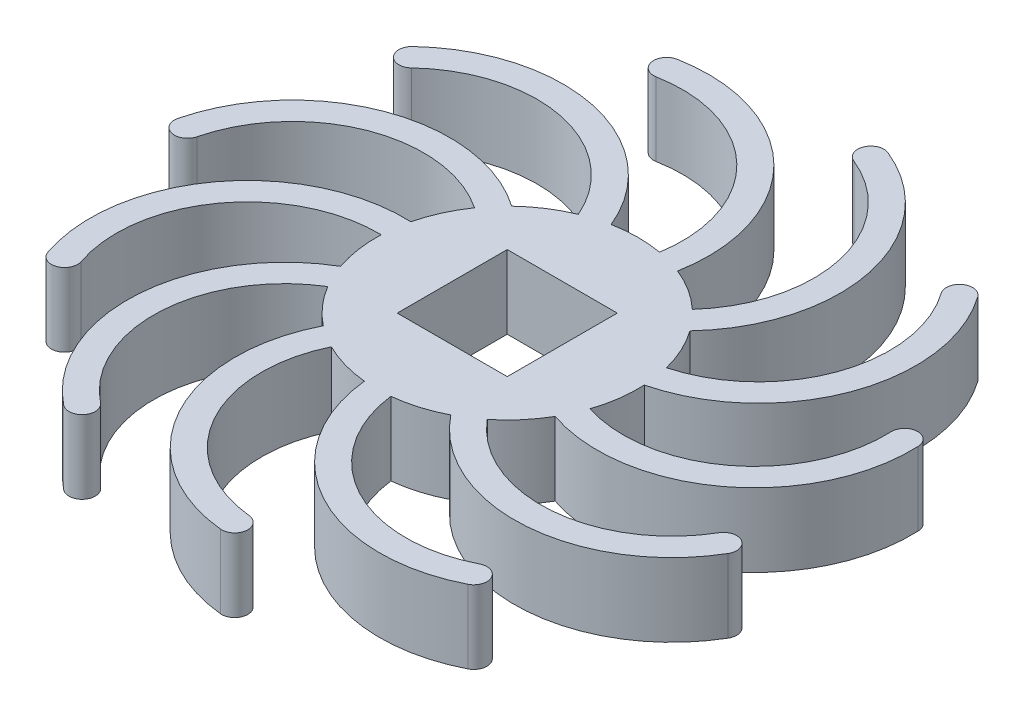
SolidWorks part; units mm, degrees
ref_plane "Front Plane" through (0, 0, 0) normal (0, 0, 1) x (1, 0, 0)
ref_plane "Top Plane" through (0, 0, 0) normal (0, 1, 0) x (1, 0, 0)
ref_plane "Right Plane" through (0, 0, 0) normal (1, 0, 0) x (0, 0, -1)
sketch "Sketch1" plane through (0, 0, 0) normal (0, 1, 0) x (1, 0, 0)
  line L0 (0, 5) -> (5.1962, 8) construction
  line L1 (-2.1, 2.1) -> (2.1, 2.1)
  line L2 (-2.1, 2.1) -> (-2.1, -2.1)
  line L3 (-2.1, -2.1) -> (2.1, -2.1)
  line L4 (2.1, 2.1) -> (2.1, -2.1)
  line L5 (0, -2.1) -> (0, 2.1) construction
  line L6 (-2.1, 0) -> (2.1, 0) construction
  line L7 (5.1962, 8) -> (5.1962, 7.3) construction
  line L8 (5.1962, 7.3) -> (0, 4.3) construction
  line L9 (0, 4.3) -> (0, 5) construction
  line L10 (2.1443, 3.7451) -> (2.4943, 4.3513) construction
  line L11 (2.4943, 4.3513) -> (8.4943, 4.3513) construction
  line L12 (8.4943, 4.3513) -> (8.1443, 3.7451) construction
  line L13 (8.1443, 3.7451) -> (2.1443, 3.7451) construction
  line L14 (3.7239, 2.1924) -> (4.3301, 2.5424) construction
  line L15 (4.3301, 2.5424) -> (9.5263, -0.4576) construction
  line L16 (9.5263, -0.4576) -> (8.9201, -0.8076) construction
  line L17 (8.9201, -0.8076) -> (3.7239, 2.1924) construction
  line L18 (4.3155, 0.058) -> (5.0155, 0.058) construction
  line L19 (5.0155, 0.058) -> (8.0155, -5.1382) construction
  line L20 (8.0155, -5.1382) -> (7.3155, -5.1382) construction
  line L21 (7.3155, -5.1382) -> (4.3155, 0.058) construction
  line L22 (3.7607, -2.0863) -> (4.3669, -2.4363) construction
  line L23 (4.3669, -2.4363) -> (4.3669, -8.4363) construction
  line L24 (4.3669, -8.4363) -> (3.7607, -8.0863) construction
  line L25 (3.7607, -8.0863) -> (3.7607, -2.0863) construction
  line L26 (2.208, -3.6659) -> (2.558, -4.2721) construction
  line L27 (2.558, -4.2721) -> (-0.442, -9.4683) construction
  line L28 (-0.442, -9.4683) -> (-0.792, -8.8621) construction
  line L29 (-0.792, -8.8621) -> (2.208, -3.6659) construction
  line L30 (0.0735, -4.2576) -> (0.0735, -4.9576) construction
  line L31 (0.0735, -4.9576) -> (-5.1226, -7.9576) construction
  line L32 (-5.1226, -7.9576) -> (-5.1226, -7.2576) construction
  line L33 (-5.1226, -7.2576) -> (0.0735, -4.2576) construction
  line L34 (-2.0708, -3.7027) -> (-2.4208, -4.3089) construction
  line L35 (-2.4208, -4.3089) -> (-8.4208, -4.3089) construction
  line L36 (-8.4208, -4.3089) -> (-8.0708, -3.7027) construction
  line L37 (-8.0708, -3.7027) -> (-2.0708, -3.7027) construction
  line L38 (-3.6504, -2.15) -> (-4.2566, -2.5) construction
  line L39 (-4.2566, -2.5) -> (-9.4528, 0.5) construction
  line L40 (-9.4528, 0.5) -> (-8.8465, 0.85) construction
  line L41 (-8.8465, 0.85) -> (-3.6504, -2.15) construction
  line L42 (-4.242, -0.0155) -> (-4.942, -0.0155) construction
  line L43 (-4.942, -0.0155) -> (-7.942, 5.1806) construction
  line L44 (-7.942, 5.1806) -> (-7.242, 5.1806) construction
  line L45 (-7.242, 5.1806) -> (-4.242, -0.0155) construction
  line L46 (-3.6872, 2.1288) -> (-4.2934, 2.4788) construction
  line L47 (-4.2934, 2.4788) -> (-4.2934, 8.4788) construction
  line L48 (-4.2934, 8.4788) -> (-3.6872, 8.1288) construction
  line L49 (-3.6872, 8.1288) -> (-3.6872, 2.1288) construction
  line L50 (-2.1345, 3.7084) -> (-2.4845, 4.3146) construction
  line L51 (-2.4845, 4.3146) -> (0.5155, 9.5107) construction
  line L52 (0.5155, 9.5107) -> (0.8655, 8.9045) construction
  line L53 (0.8655, 8.9045) -> (-2.1345, 3.7084) construction
  circle A0 centre (0, 0) radius 5
  point P62 (0.0368, 0.0212)
  dimension "D1" = 10
  dimension "D2" = 4.2
  dimension "D3" = 4.2
  dimension "D4" = 0.7
  dimension "D5" = 120
  dimension "D6" = 6
  dimension "D7" = 12
extrude "Boss-Extrude1" add sketch "Sketch1" along normal blind 2.8
sketch "Sketch2" plane through (0, 0, 0) normal (0, 1, 0) x (1, 0, 0)
  line L0 (0, -5) -> (7.99, -9.613) construction
  line L1 (7.99, -9.613) -> (7.99, -8.9202) construction
  line L2 (7.99, -8.9202) -> (0, -4.3072) construction
  line L3 (0, -4.3072) -> (0, -5) construction
  line L4 (0, 0) -> (0, -5) construction
  line L5 (-2.1536, -3.7301) -> (-2.5, -4.3301) construction
  line L6 (-2.1, -2.1) -> (2.1, -2.1) construction
  line L7 (-2.1, -2.1) -> (-2.1, 2.1) construction
  line L8 (-2.1, 2.1) -> (2.1, 2.1) construction
  line L9 (2.1, -2.1) -> (2.1, 2.1) construction
  line L10 (0, 2.1) -> (0, -2.1) construction
  line L11 (-2.1, 0) -> (2.1, 0) construction
  line L12 (-2.5, -4.3301) -> (2.113, -12.3201) construction
  line L13 (2.113, -12.3201) -> (2.4594, -11.7201) construction
  line L14 (2.4594, -11.7201) -> (-2.1536, -3.7301) construction
  line L15 (-3.7301, -2.1536) -> (-4.3301, -2.5) construction
  line L16 (-4.3301, -2.5) -> (-4.3301, -11.726) construction
  line L17 (-4.3301, -11.726) -> (-3.7301, -11.3796) construction
  line L18 (-3.7301, -11.3796) -> (-3.7301, -2.1536) construction
  line L19 (-4.3072, 0) -> (-5, 0) construction
  line L20 (-5, 0) -> (-9.613, -7.99) construction
  line L21 (-9.613, -7.99) -> (-8.9202, -7.99) construction
  line L22 (-8.9202, -7.99) -> (-4.3072, 0) construction
  line L23 (-3.7301, 2.1536) -> (-4.3301, 2.5) construction
  line L24 (-4.3301, 2.5) -> (-12.3201, -2.113) construction
  line L25 (-12.3201, -2.113) -> (-11.7201, -2.4594) construction
  line L26 (-11.7201, -2.4594) -> (-3.7301, 2.1536) construction
  line L27 (-2.1536, 3.7301) -> (-2.5, 4.3301) construction
  line L28 (-2.5, 4.3301) -> (-11.726, 4.3301) construction
  line L29 (-11.726, 4.3301) -> (-11.3796, 3.7301) construction
  line L30 (-11.3796, 3.7301) -> (-2.1536, 3.7301) construction
  line L31 (0, 4.3072) -> (0, 5) construction
  line L32 (0, 5) -> (-7.99, 9.613) construction
  line L33 (-7.99, 9.613) -> (-7.99, 8.9202) construction
  line L34 (-7.99, 8.9202) -> (0, 4.3072) construction
  line L35 (2.1536, 3.7301) -> (2.5, 4.3301) construction
  line L36 (2.5, 4.3301) -> (-2.113, 12.3201) construction
  line L37 (-2.113, 12.3201) -> (-2.4594, 11.7201) construction
  line L38 (-2.4594, 11.7201) -> (2.1536, 3.7301) construction
  line L39 (3.7301, 2.1536) -> (4.3301, 2.5) construction
  line L40 (4.3301, 2.5) -> (4.3301, 11.726) construction
  line L41 (4.3301, 11.726) -> (3.7301, 11.3796) construction
  line L42 (3.7301, 11.3796) -> (3.7301, 2.1536) construction
  line L43 (4.3072, 0) -> (5, 0) construction
  line L44 (5, 0) -> (9.613, 7.99) construction
  line L45 (9.613, 7.99) -> (8.9202, 7.99) construction
  line L46 (8.9202, 7.99) -> (4.3072, 0) construction
  line L47 (3.7301, -2.1536) -> (4.3301, -2.5) construction
  line L48 (4.3301, -2.5) -> (12.3201, 2.113) construction
  line L49 (12.3201, 2.113) -> (11.7201, 2.4594) construction
  line L50 (11.7201, 2.4594) -> (3.7301, -2.1536) construction
  line L51 (2.1536, -3.7301) -> (2.5, -4.3301) construction
  line L52 (2.5, -4.3301) -> (11.726, -4.3301) construction
  line L53 (11.726, -4.3301) -> (11.3796, -3.7301) construction
  line L54 (11.3796, -3.7301) -> (2.1536, -3.7301) construction
  line L55 (7.99, -9.2666) -> (0, -4.6536) construction
  line L56 (3.995, -6.9601) -> (5.495, -4.362) construction
  circle A0 centre (0, 0) radius 5 construction
  arc A1 (0, -4.6536) -> (7.99, -9.2666) centre (5.495, -4.362) ccw construction
  arc A2 (-0.4993, -4.6801) -> (8.2167, -9.7123) centre (5.495, -4.362) ccw
  arc A3 (0.4993, -4.6271) -> (7.7633, -8.821) centre (5.495, -4.362) ccw
  arc A4 (0.4993, -4.6271) -> (-0.4993, -4.6801) centre (0, -4.6536) ccw
  arc A5 (8.2167, -9.7123) -> (7.7633, -8.821) centre (7.99, -9.2666) ccw
  arc A6 (-2.0816, -4.1625) -> (1.7619, -11.6178) centre (2.2644, -6.6404) ccw
  arc A7 (-2.0816, -4.1625) -> (-2.9503, -3.6672) centre (-2.5159, -3.9148) ccw
  arc A8 (1.6615, -12.6128) -> (1.7619, -11.6178) centre (1.7117, -12.1153) ccw
  arc A9 (-2.9503, -3.6672) -> (1.6615, -12.6128) centre (2.2644, -6.6404) ccw
  arc A10 (-2.5159, -3.9148) -> (1.7117, -12.1153) centre (2.2644, -6.6404) ccw construction
  arc A11 (-4.0015, -2.3763) -> (-4.7988, -10.7261) centre (-1.6851, -6.8105) ccw
  arc A12 (-4.0015, -2.3763) -> (-4.4646, -1.49) centre (-4.2331, -1.9332) ccw
  arc A13 (-5.4212, -11.5088) -> (-4.7988, -10.7261) centre (-5.11, -11.1174) ccw
  arc A14 (-4.4646, -1.49) -> (-5.4212, -11.5088) centre (-1.6851, -6.8105) ccw
  arc A15 (-4.2331, -1.9332) -> (-5.11, -11.1174) centre (-1.6851, -6.8105) ccw construction
  arc A16 (-4.6511, 0.1643) -> (-9.836, -6.4289) centre (-5.0996, -4.8183) ccw
  arc A17 (-4.6511, 0.1643) -> (-4.5614, 1.1603) centre (-4.6062, 0.6623) ccw
  arc A18 (-10.7828, -6.7509) -> (-9.836, -6.4289) centre (-10.3094, -6.5899) ccw
  arc A19 (-4.5614, 1.1603) -> (-10.7828, -6.7509) centre (-5.0996, -4.8183) ccw
  arc A20 (-4.6062, 0.6623) -> (-10.3094, -6.5899) centre (-5.0996, -4.8183) ccw construction
  arc A21 (-3.8239, 2.6528) -> (-11.7503, -0.0906) centre (-6.8951, -1.2963) ccw
  arc A22 (-3.8239, 2.6528) -> (-3.21, 3.4421) centre (-3.5169, 3.0475) ccw
  arc A23 (-12.7208, 0.1504) -> (-11.7503, -0.0906) centre (-12.2356, 0.0299) ccw
  arc A24 (-3.21, 3.4421) -> (-12.7208, 0.1504) centre (-6.8951, -1.2963) ccw
  arc A25 (-3.5169, 3.0475) -> (-12.2356, 0.0299) centre (-6.8951, -1.2963) ccw construction
  arc A26 (-1.7827, 4.299) -> (-9.934, 6.2765) centre (-6.5013, 2.6372) ccw
  arc A27 (-1.7827, 4.299) -> (-0.8395, 4.6312) centre (-1.3111, 4.4651) ccw
  arc A28 (-10.6201, 7.0039) -> (-9.934, 6.2765) centre (-10.277, 6.6402) ccw
  arc A29 (-0.8395, 4.6312) -> (-10.6201, 7.0039) centre (-6.5013, 2.6372) ccw
  arc A30 (-1.3111, 4.4651) -> (-10.277, 6.6402) centre (-6.5013, 2.6372) ccw construction
  arc A31 (0.8245, 4.5803) -> (-4.9637, 10.6508) centre (-4.0435, 5.7334) ccw
  arc A32 (0.8245, 4.5803) -> (1.7976, 4.3498) centre (1.3111, 4.4651) ccw
  arc A33 (-5.1476, 11.6338) -> (-4.9637, 10.6508) centre (-5.0556, 11.1423) ccw
  arc A34 (1.7976, 4.3498) -> (-5.1476, 11.6338) centre (-4.0435, 5.7334) ccw
  arc A35 (1.3111, 4.4651) -> (-5.0556, 11.1423) centre (-4.0435, 5.7334) ccw construction
  arc A36 (3.17, 3.4074) -> (1.5826, 11.6436) centre (-0.3019, 7.0094) ccw
  arc A37 (3.17, 3.4074) -> (3.8639, 2.6875) centre (3.5169, 3.0475) ccw
  arc A38 (1.9592, 12.5699) -> (1.5826, 11.6436) centre (1.7709, 12.1068) ccw
  arc A39 (3.8639, 2.6875) -> (1.9592, 12.5699) centre (-0.3019, 7.0094) ccw
  arc A40 (3.5169, 3.0475) -> (1.7709, 12.1068) centre (-0.3019, 7.0094) ccw construction
  arc A41 (4.5089, 1.1527) -> (7.6263, 8.9396) centre (3.5356, 6.0598) ccw
  arc A42 (4.5089, 1.1527) -> (4.7035, 0.1718) centre (4.6062, 0.6623) ccw
  arc A43 (8.444, 9.5153) -> (7.6263, 8.9396) centre (8.0352, 9.2274) ccw
  arc A44 (4.7035, 0.1718) -> (8.444, 9.5153) centre (3.5356, 6.0598) ccw
  arc A45 (4.6062, 0.6623) -> (8.0352, 9.2274) centre (3.5356, 6.0598) ccw construction
  arc A46 (4.4164, -1.468) -> (11.2488, 3.3974) centre (6.2505, 3.1864) ccw
  arc A47 (4.4164, -1.468) -> (4.0497, -2.3984) centre (4.2331, -1.9332) ccw
  arc A48 (12.2479, 3.4395) -> (11.2488, 3.3974) centre (11.7484, 3.4185) ccw
  arc A49 (4.0497, -2.3984) -> (12.2479, 3.4395) centre (6.2505, 3.1864) ccw
  arc A50 (4.2331, -1.9332) -> (11.7484, 3.4185) centre (6.2505, 3.1864) ccw construction
  arc A51 (2.9216, -3.6226) -> (11.2999, -3.2235) centre (6.981, -0.6988) ccw
  arc A52 (2.9216, -3.6226) -> (2.1102, -4.2071) centre (2.5159, -3.9148) ccw
  arc A53 (12.1632, -3.7282) -> (11.2999, -3.2235) centre (11.7315, -3.4759) ccw
  arc A54 (2.1102, -4.2071) -> (12.1632, -3.7282) centre (6.981, -0.6988) ccw
  arc A55 (2.5159, -3.9148) -> (11.7315, -3.4759) centre (6.981, -0.6988) ccw construction
  point P58 (0, 0)
  point P61 (2.7436, -9.1275)
  point P72 (-2.6266, -9.1619)
  point P80 (-7.1629, -6.2874)
  point P88 (-9.4251, -1.4167)
  point P96 (-8.6948, 3.9038)
  point P104 (-5.204, 7.9848)
  point P112 (-0.061, 9.5308)
  point P120 (5.1014, 8.0508)
  point P128 (8.6442, 4.0147)
  point P136 (9.4424, -1.296)
  point P144 (7.2428, -6.1952)
  point P149 (0, 0)
  dimension "D7" = 0.5
  dimension "D1" = 0.6
  dimension "D2" = 12.5
  dimension "D3" = 5
  dimension "D4" = 120
  dimension "D6" = 3
  dimension "D5" = 12
  dimension "D8" = 11
extrude "Boss-Extrude5" add sketch "Sketch2" along normal blind 2.8
